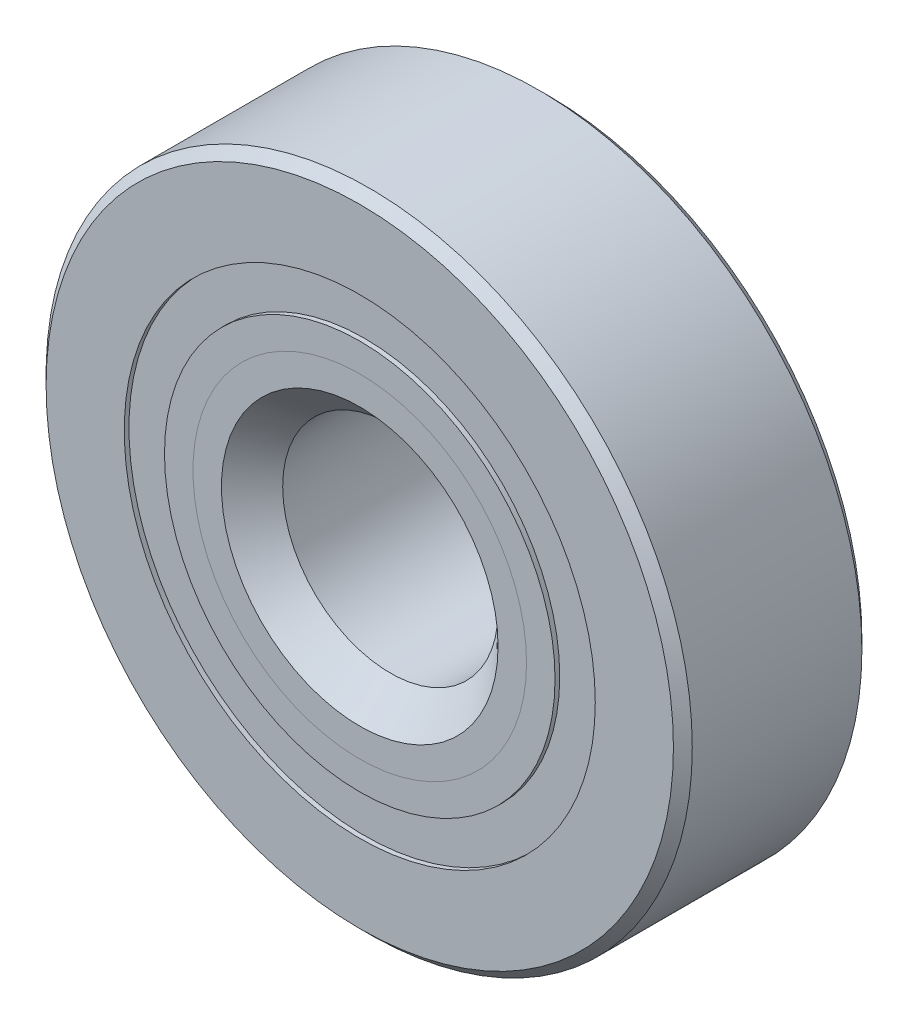
SolidWorks part; units mm, degrees
ref_plane "Front Plane" through (0, 0, 0) normal (0, 0, 1) x (1, 0, 0)
ref_plane "Top Plane" through (0, 0, 0) normal (0, 1, 0) x (1, 0, 0)
ref_plane "Right Plane" through (0, 0, 0) normal (1, 0, 0) x (0, 0, -1)
sketch "Sketch1" plane through (0, 0, 0) normal (1, 0, 0) x (0, 0, -1)
  line L0 (-2.7781, 0) -> (2.7781, 0) construction
  line L1 (0, 9.525) -> (0, -9.525) construction
  line L2 (2.5003, 9.525) -> (-2.5003, 9.525)
  line L3 (-2.5003, 9.525) -> (-2.7781, 9.2472)
  line L4 (-2.7781, 9.2472) -> (-2.7781, 6.9431)
  line L5 (-2.7781, 6.9431) -> (-1.2347, 6.9431)
  line L6 (2.7781, 6.9431) -> (1.2347, 6.9431)
  line L7 (2.7781, 9.2472) -> (2.7781, 6.9431)
  line L8 (2.5003, 9.525) -> (2.7781, 9.2472)
  line L9 (0, 9.525) -> (0, 6.35) construction
  line L10 (0, 6.35) -> (0, 3.175) construction
  arc A0 (-1.2347, 6.9431) -> (1.2347, 6.9431) centre (0, 6.35) cw
  point P14 (0, 3.175)
  dimension "D3" = 2.4694
  dimension "D1" = 45
  dimension "Width" = 5.5562
  dimension "OD" = 19.05
  dimension "D2" = 0.2778
  dimension "Shaft Dia" = 6.35
  dimension "D4" = 0.5931
revolve "Revolve1" add sketch "Sketch1" angle 360 about L0
sketch "Sketch2" plane through (0, 0, 0) normal (1, 0, 0) x (0, 0, -1)
  line L0 (-2.7781, 5.7569) -> (-1.2347, 5.7569)
  line L1 (-2.7781, 9.2472) -> (-2.7781, -9.2472) construction
  line L2 (-2.7781, 5.7569) -> (-2.7781, 4.9172)
  line L3 (-2.7781, 4.9172) -> (-1.9385, 4.0776)
  line L4 (-1.9385, 4.0776) -> (0, 4.0776)
  line L5 (0, 9.525) -> (0, -9.525) construction
  line L6 (0, 4.0776) -> (0, 4.9802)
  line L7 (0, 4.9802) -> (0, 3.175) construction
  line L8 (-2.7781, 5.7569) -> (-2.7781, 4.0776) construction
  line L9 (-2.7781, 4.0776) -> (-1.9385, 4.0776) construction
  arc A0 (-1.2347, 5.7569) -> (0, 4.9802) centre (0, 6.35) ccw
  arc A1 (1.2347, 6.9431) -> (-1.2347, 6.9431) centre (0, 6.35) ccw construction
  circle A2 centre (0, 6.35) radius 1.3698 construction
  dimension "D1" = 45
revolve "Revolve2" add sketch "Sketch2" angle 360 about L0
sketch "Sketch3" plane through (0, 0, 0) normal (1, 0, 0) x (0, 0, -1)
  line L0 (-2.7781, 4.9172) -> (-1.9385, 4.0776)
  line L1 (-1.9385, 4.0776) -> (0, 4.0776)
  line L2 (0, 4.0776) -> (0, 4.9802)
  line L3 (-2.7781, 4.9172) -> (-2.7781, 4.0776)
  line L4 (-2.7781, 5.7569) -> (-2.7781, 4.0776) construction
  line L5 (-2.7781, 4.0776) -> (-1.8755, 3.175)
  line L6 (-1.8755, 3.175) -> (2.5003, 3.175)
  line L7 (2.5003, 9.525) -> (2.5003, -9.525) construction
  line L8 (2.5003, 3.175) -> (2.7781, 3.4528)
  line L9 (2.7781, -9.2472) -> (2.7781, 9.2472) construction
  line L10 (2.7781, 3.4528) -> (2.7781, 5.7569)
  line L11 (2.7781, 5.7569) -> (1.2347, 5.7569)
  line L13 (2.5003, 9.525) -> (2.7781, 9.2472) construction
  circle A0 centre (0, 6.35) radius 1.3698 construction
  arc A1 (1.2347, 5.7569) -> (0, 4.9802) centre (0, 6.35) cw
revolve "Revolve3" add sketch "Sketch3" angle 360 about L0
sketch "Sketch4" plane through (0, 0, 0) normal (1, 0, 0) x (0, 0, -1)
  line L0 (-1.3698, 6.35) -> (1.3698, 6.35)
  circle A1 centre (0, 6.35) radius 1.3698 construction
  arc A2 (-1.3698, 6.35) -> (1.3698, 6.35) centre (0, 6.35) cw
  arc A3 (1.2347, 6.9431) -> (-1.2347, 6.9431) centre (0, 6.35) ccw construction
revolve "Revolve4" add sketch "Sketch4" angle 360 about L0
ref_axis "Axis1" through (0, 0, -2.7781) along (0, 0, 1)
pattern_circular "CirPattern1" count 10 every 36 about axis through (0, 0, -2.7781) along (0, 0, 1) of bodies 104
sketch "Sketch5" plane through (0, 0, 0) normal (1, 0, 0) x (0, 0, -1)
  line L0 (-2.7781, 6.9431) -> (-1.2347, 6.9431) construction
  line L1 (-2.6392, 6.9431) -> (-1.3698, 6.9431)
  line L2 (-2.6392, 6.9431) -> (-2.6392, 5.7569)
  line L3 (-2.6392, 5.7569) -> (-1.3698, 5.7569)
  line L4 (-1.3698, 6.9431) -> (-1.3698, 5.7569)
  line L5 (1.3698, 6.9431) -> (2.6392, 6.9431)
  line L6 (1.3698, 6.9431) -> (1.3698, 5.7569)
  line L7 (1.3698, 5.7569) -> (2.6392, 5.7569)
  line L8 (2.6392, 6.9431) -> (2.6392, 5.7569)
  line L9 (-2.7781, 5.7569) -> (-1.2347, 5.7569) construction
  line L10 (-2.6392, 9.3861) -> (-2.6392, 6.9431) construction
  line L11 (-2.5003, 9.525) -> (-2.7781, 9.2472) construction
  circle A0 centre (0, 6.35) radius 1.3698 construction
revolve "Revolve5" add sketch "Sketch5" angle 360 about L0
equation "\"D2@Sketch1\" = \"Width@Sketch1\"*.05"
equation "\"D3@Sketch1\" = \"Width@Sketch1\"/2.25"
equation "\"D4@Sketch1\" = (((\"OD@Sketch1\"-\"Width@Sketch1\")/2)/3.25)/3.5"
equation "\"D2@CirPattern1\" = 360/\"Balls@CirPattern1\""
